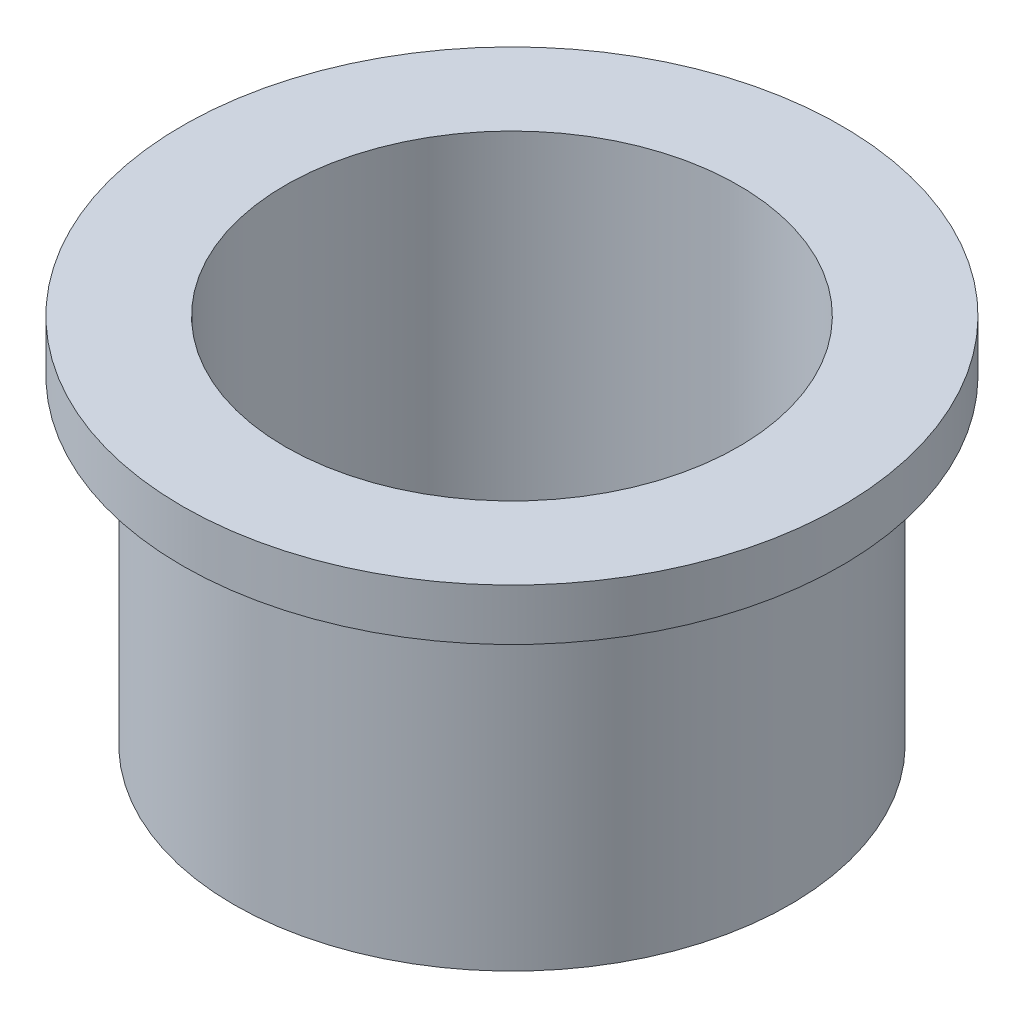
SolidWorks part; units mm, degrees
ref_plane "Front Plane" through (0, 0, 0) normal (0, 0, 1) x (1, 0, 0)
ref_plane "Top Plane" through (0, 0, 0) normal (0, 1, 0) x (1, 0, 0)
ref_plane "Right Plane" through (0, 0, 0) normal (1, 0, 0) x (0, 0, -1)
sketch "Sketch1" plane through (0, 0, 0) normal (0, 1, 0) x (1, 0, 0)
  circle A0 centre (0, 0) radius 13.5
  circle A1 centre (0, 0) radius 11
  dimension "D1" = 22
  dimension "D2" = 27
extrude "Boss-Extrude1" add sketch "Sketch1" along normal blind 18
sketch "Sketch2" plane through (0, 18, 0) normal (0, 1, 0) x (1, 0, 0)
  circle A0 centre (0, 0) radius 16
  circle A1 centre (0, 0) radius 13.5
  circle A2 centre (0, 0) radius 13.5 construction
  dimension "D1" = 32
extrude "Boss-Extrude2" add sketch "Sketch2" against normal blind 2.5
equation "\"inner_diameter\"=22.00"
equation "\"outer_diameter\"=27.00"
equation "\"length\"=18.00"
equation "\"flange_thickness\"=2.50"
equation "\"flange_diameter\"=32.00"
equation "\"D1@Sketch1\"=\"inner_diameter\""
equation "\"D2@Sketch1\"=\"outer_diameter\""
equation "\"D1@Boss-Extrude1\"=\"length\""
equation "\"D1@Sketch2\"=\"flange_diameter\""
equation "\"D1@Boss-Extrude2\"=\"flange_thickness\""
